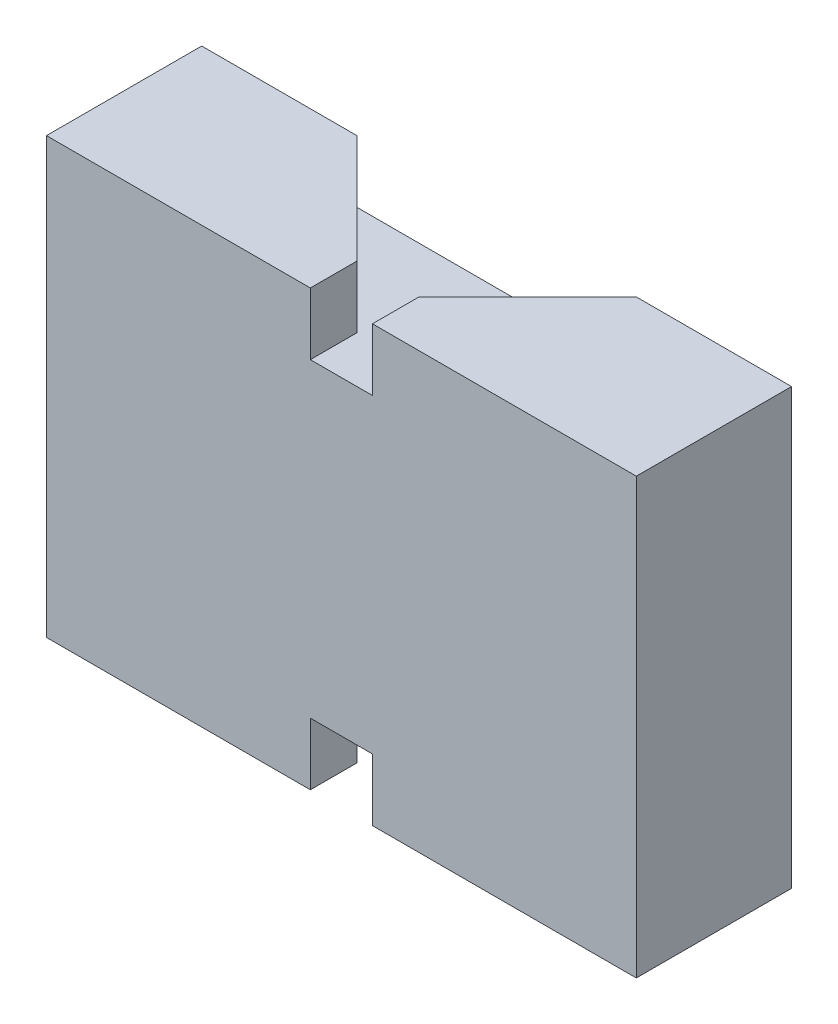
SolidWorks part; units mm, degrees
ref_plane "Front Plane" through (0, 0, 0) normal (0, 0, 1) x (1, 0, 0)
ref_plane "Top Plane" through (0, 0, 0) normal (0, 1, 0) x (1, 0, 0)
ref_plane "Right Plane" through (0, 0, 0) normal (1, 0, 0) x (0, 0, -1)
sketch "Sketch1" plane through (0, 0, 0) normal (0, 0, 1) x (1, 0, 0)
  line L1 (-95, -70) -> (95, -70)
  line L2 (-95, -70) -> (-95, 70)
  line L3 (-95, 70) -> (95, 70)
  line L4 (95, -70) -> (95, 70)
  line L5 (-95, -70) -> (95, 70) construction
  line L6 (-95, 70) -> (95, -70) construction
  point P0 (0, 0)
extrude "Boss-Extrude1" add sketch "Sketch1" along normal blind 50
sketch "Sketch2" plane through (0, -70, 0) normal (0, -1, 0) x (-1, 0, 0)
  line L0 (0, -50) -> (0, 0) construction
  line L1 (95, -50) -> (-95, -50) construction
  line L2 (95, 0) -> (-95, 0) construction
  line L3 (-10, -50) -> (10, -50)
  line L4 (45, 0) -> (-45, 0)
  line L5 (10, -50) -> (10, -35)
  line L6 (10, -35) -> (45, 0)
  line L7 (-10, -35) -> (-45, 0)
  line L8 (-10, -50) -> (-10, -35)
  dimension "D1" = 15
  dimension "D2" = 45
extrude "Cut-Extrude1" cut sketch "Sketch2" against normal blind 20
sketch "Sketch3" plane through (0, 0, 50) normal (0, 0, 1) x (1, 0, 0)
  line L0 (-95, 0) -> (95, 0) construction
  line L1 (-95, 70) -> (-95, -70) construction
  line L2 (95, -70) -> (95, 70) construction
ref_plane "Plane1" through (0, 0, 0) normal (0, -1, 0) x (1, 0, 0)
mirror "Mirror1" about plane through (0, 0, 0) normal (0, -1, 0) of "Cut-Extrude1"
sketch "Sketch4" plane through (0, 0, 50) normal (0, 0, 1) x (1, 0, 0)
  line L0 (-95, 0) -> (95, 0) construction
  line L1 (-95, 70) -> (-95, -70) construction
  line L2 (95, -70) -> (95, 70) construction
